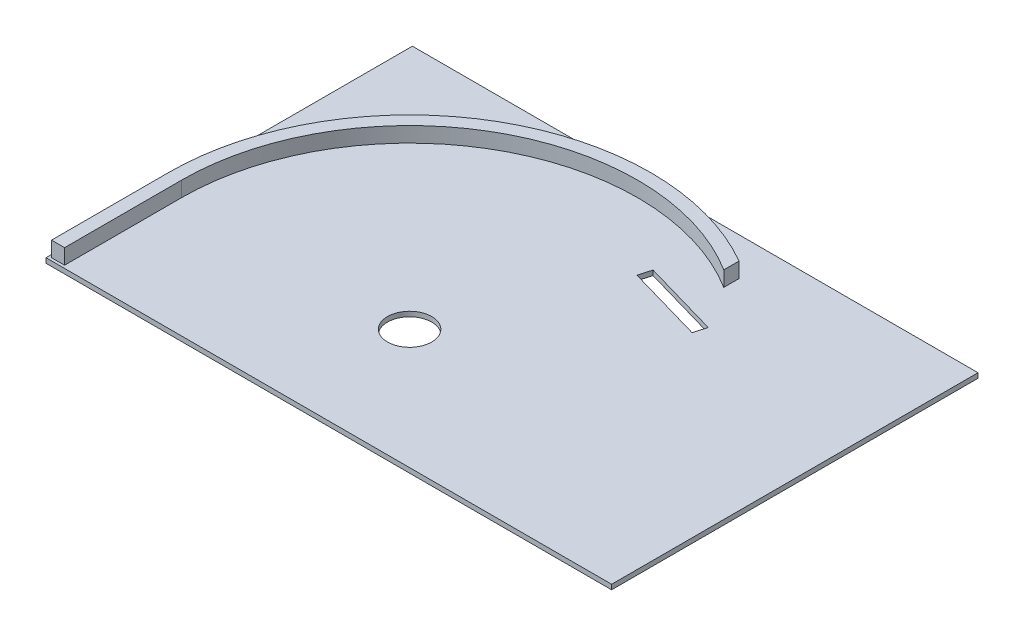
SolidWorks part; units mm, degrees
material "Particle Board"
ref_plane "Front Plane" through (0, 0, 0) normal (0, 0, 1) x (1, 0, 0)
ref_plane "Top Plane" through (0, 0, 0) normal (0, 1, 0) x (1, 0, 0)
ref_plane "Right Plane" through (0, 0, 0) normal (1, 0, 0) x (0, 0, -1)
sketch "Sketch3" plane through (0, 0, 0) normal (0, 1, 0) x (1, 0, 0)
  line L1 (0, 0) -> (-839.8654, 0) construction
  line L2 (0, 0) -> (-451.1992, 260.5) construction
  line L5 (-524, 0) -> (-554, 0)
  line L6 (277.6777, 444.3772) -> (277.6777, 479.3862)
  circle A0 centre (0, 0) radius 254 construction
  arc A3 (277.6777, 444.3772) -> (-524, 0) centre (0, 0) ccw
  arc A4 (277.6777, 479.3862) -> (-554, 0) centre (0, 0) ccw
  arc A5 (293.5753, 469.8186) -> (-554, 0) centre (0, 0) ccw construction
  dimension "D1" = 524
  dimension "D2" = 30
  dimension "D4" = 122
  dimension "D5" = 508
  dimension "D3" = 30
extrude "Boss-Extrude1" add sketch "Sketch3" along normal blind 35
sketch "Sketch4" plane through (0, 0, 0) normal (0, 1, 0) x (1, 0, 0)
  line L0 (-538.2597, 554) -> (609.3192, 554) construction
  line L5 (-560.35, 566.7) -> (739.65, 566.7)
  line L6 (-560.35, 566.7) -> (-560.35, -275.4)
  line L7 (-560.35, -275.4) -> (739.65, -275.4)
  line L8 (739.65, 566.7) -> (739.65, -275.4)
  arc A0 (277.6777, 479.3862) -> (-554, 0) centre (0, 0) ccw construction
  dimension "D1" = 275.4
  dimension "D2" = 6.35
  dimension "D3" = 12.7
  dimension "D4" = 1300
extrude "Boss-Extrude2" add sketch "Sketch4" against normal blind 11.1125
hole_wizard "Ø20.0mm Dowel Hole1" positions "Sketch6" profile "Sketch7" hole size "Ø20.0" standard "ANSI Metric" end condition through all
sketch "Sketch6" plane through (0, 0, 0) normal (0, 1, 0) x (1, 0, 0)
  point P0 (0, 0)
sketch "Sketch7" plane through (0, 0, 0) normal (1, 0, 0) x (0, 0, 1)
  line L0 (0, 0) -> (0, 11.1125)
  line L1 (0, 11.1125) -> (50.8, 11.1125)
  line L2 (50.8, 11.1125) -> (50.8, 0)
  line L5 (50.8, 0) -> (0, 0)
  line L11 (0, -6.35) -> (0, 107.95) construction
  dimension "Thru Hole Dia." = 101.6
  dimension "Thru Hole Depth" = 11.1125
ref_plane "Plane1" through (0, 0, 269.05) normal (0, 0, 1) x (1, 0, 0)
sketch "Sketch8" plane through (0, 0, 0) normal (0, 0, 1) x (1, 0, 0)
  line L1 (-554, 35) -> (-524, 35)
  line L2 (-554, 35) -> (-554, 0)
  line L3 (-554, 0) -> (-524, 0)
  line L4 (-524, 35) -> (-524, 0)
extrude "Boss-Extrude3" add sketch "Sketch8" along normal up to surface (269.05 mm away) up to plane "Plane1"
sketch "Sketch9" plane through (0, 0, 0) normal (0, 1, 0) x (1, 0, 0)
  line L0 (339.65, 346.7) -> (161.8166, 397.6929)
  line L1 (161.8166, 397.6929) -> (153.5475, 368.8551)
  line L2 (153.5475, 368.8551) -> (331.3809, 317.8621)
  line L3 (331.3809, 317.8621) -> (339.65, 346.7)
  line L4 (739.65, 566.7) -> (-560.35, 566.7) construction
  line L5 (739.65, -275.4) -> (739.65, 566.7) construction
  dimension "D1" = 185
  dimension "D2" = 30
  dimension "D3" = 16
  dimension "D4" = 400
  dimension "D5" = 220
extrude "Cut-Extrude1" cut sketch "Sketch9" against normal through all
